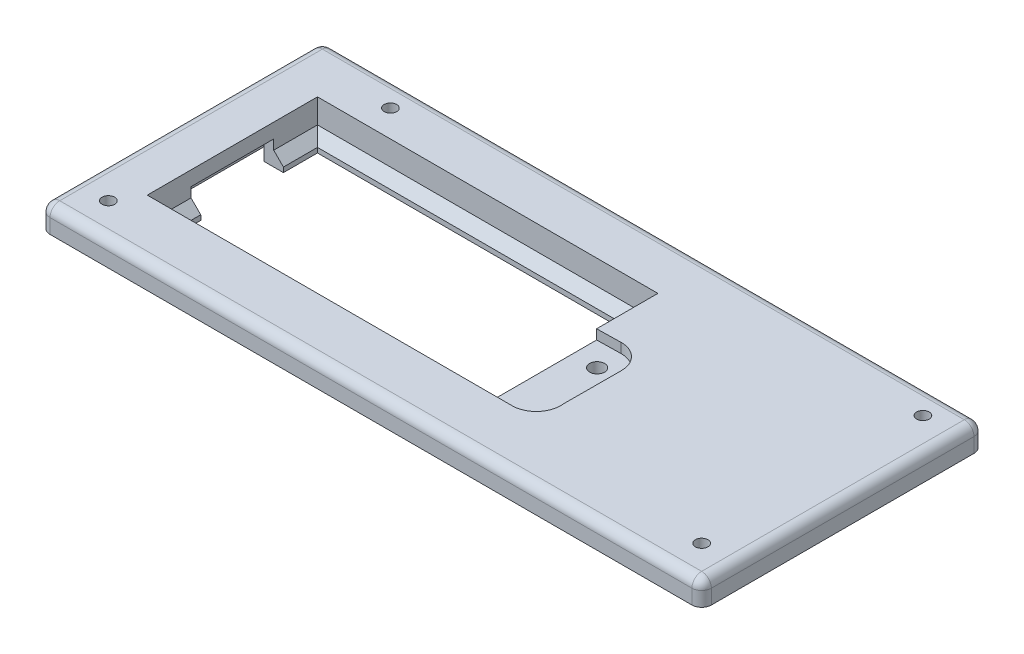
SolidWorks part; units mm, degrees
ref_plane "Front Plane" through (0, 0, 0) normal (0, 0, 1) x (1, 0, 0)
ref_plane "Top Plane" through (0, 0, 0) normal (0, 1, 0) x (1, 0, 0)
ref_plane "Right Plane" through (0, 0, 0) normal (1, 0, 0) x (0, 0, -1)
sketch "Sketch1" plane through (0, 0, 0) normal (0, 1, 0) x (1, 0, 0)
  line L1 (0, 73.66) -> (172.72, 73.66)
  line L2 (0, 73.66) -> (0, 0)
  line L3 (0, 0) -> (172.72, 0)
  line L4 (172.72, 73.66) -> (172.72, 0)
  circle A0 centre (24.765, 66.675) radius 1.6319
  circle A1 centre (8.89, 8.89) radius 1.6319
  circle A2 centre (163.83, 66.675) radius 1.632
  circle A4 centre (163.83, 8.89) radius 1.632
  dimension "D3" = 3.2639
  dimension "D4" = 0
  dimension "D5" = 0
  dimension "D13" = 6.985
  dimension "D14" = 24.765
  dimension "D1" = 172.72
  dimension "D2" = 73.66
  dimension "D7" = 8.89
  dimension "D8" = 8.89
  dimension "D9" = 8.89
  dimension "D10" = 8.89
  dimension "D11" = 6.985
  dimension "D12" = 8.89
extrude "Boss-Extrude1" add sketch "Sketch1" along normal blind 6.35
sketch "Sketch2" plane through (0, 6.35, 0) normal (0, 1, 0) x (1, 0, 0)
  line L0 (172.72, 73.66) -> (0, 73.66) construction
  line L1 (101.6, 59.69) -> (12.7, 59.69)
  line L2 (101.6, 59.69) -> (101.6, 15.24)
  line L3 (101.6, 15.24) -> (12.7, 15.24)
  line L4 (12.7, 59.69) -> (12.7, 15.24)
  line L5 (0, 73.66) -> (0, 0) construction
  dimension "D1" = 44.45
  dimension "D2" = 13.97
  dimension "D3" = 88.9
  dimension "D4" = 12.7
extrude "Cut-Extrude1" cut sketch "Sketch2" against normal blind 6.35
fillet "Fillet1" radius 2.54 8 edges at (172.72, 3.175, -73.66) (172.72, 3.175, 0) (172.72, 6.35, -36.83) (0, 3.175, 0) (86.36, 6.35, 0) (0, 6.35, -36.83) (86.36, 6.35, -73.66) (0, 3.175, -73.66)
sketch "Sketch3" plane through (0, 0, 0) normal (0, -1, 0) x (1, 0, 0)
  line L0 (12.7, -15.24) -> (101.6, -15.24) construction
  line L1 (10.16, -12.7) -> (104.14, -12.7)
  line L3 (15.24, -17.78) -> (104.14, -17.78)
  line L4 (104.14, -12.7) -> (104.14, -17.78)
  line L5 (10.16, -62.23) -> (104.14, -62.23)
  line L6 (10.16, -62.23) -> (10.16, -48.26)
  line L7 (15.24, -57.15) -> (104.14, -57.15)
  line L8 (104.14, -62.23) -> (104.14, -57.15)
  line L9 (101.6, -59.69) -> (12.7, -59.69) construction
  line L10 (12.7, -59.69) -> (12.7, -15.24) construction
  line L11 (12.7, -59.69) -> (12.7, -15.24) construction
  line L14 (10.16, -26.67) -> (15.24, -26.67)
  line L15 (15.24, -17.78) -> (15.24, -26.67)
  line L18 (10.16, -48.26) -> (15.24, -48.26)
  line L19 (15.24, -57.15) -> (15.24, -48.26)
  line L22 (10.16, -26.67) -> (10.16, -12.7)
  dimension "D1" = 2.54
  dimension "D2" = 2.54
  dimension "D3" = 2.54
  dimension "D4" = 2.54
  dimension "D5" = 2.54
  dimension "D6" = 2.54
  dimension "D7" = 93.98
  dimension "D9" = 8.89
  dimension "D10" = 8.89
  dimension "D11" = 2.54
  dimension "D12" = 2.54
extrude "Boss-Extrude2" add sketch "Sketch3" along normal blind 3.81
chamfer "Chamfer1" distance 2.54 angle 45 1 edges at (12.7, 0, -37.465)
chamfer "Chamfer2" distance 2.54 angle 45 4 edges at (58.42, 0, -17.78) (15.24, 0, -22.225) (15.24, 0, -52.705) (58.42, 0, -57.15)
sketch "Sketch6" plane through (0, 6.35, 0) normal (0, 1, 0) x (1, 0, 0)
  line L0 (101.6, 15.24) -> (101.6, 59.69) construction
  line L1 (101.6, 59.69) -> (12.7, 59.69) construction
  line L2 (107.9711, 43.815) -> (107.9289, 43.815)
  line L3 (114.25, 22.385) -> (114.2999, 37.4228)
  line L4 (101.6, 37.465) -> (101.6, 21.5899)
  line L6 (107.5751, 15.2509) -> (108.3484, 15.2524)
  line L7 (107.9711, 43.815) -> (107.9289, 43.815)
  arc A0 (114.2999, 37.4228) -> (101.6, 37.465) centre (107.95, 37.465) ccw
  arc A1 (101.6, 21.5899) -> (114.25, 22.385) centre (107.95, 21.5899) ccw
  point P3 (101.6, 29.5274)
  line M9 (101.6, 59.69) -> (101.6, 15.24)
  dimension "D1" = 6.35
  dimension "D4" = 12.7
  dimension "D5" = 12.6736
  dimension "D2" = 15.0377
  dimension "D3" = 22.225
  dimension "D6" = 6.35
extrude "Cut-Extrude3" cut sketch "Sketch6" against normal blind 2.54 and the other way through all contours L6 A1 L3 A0 L2 M9 region at (107.9425, 6.35, -29.5304)
sketch "Sketch7" plane through (0, 6.35, 0) normal (0, 1, 0) x (1, 0, 0)
  line L0 (101.6, 37.465) -> (101.6, 43.6852)
  line L1 (101.6, 37.465) -> (101.6, 59.69) construction
  line L2 (101.6, 43.6852) -> (107.9711, 43.815)
  line L3 (101.6, 21.5899) -> (101.6, 15.24)
  line L4 (101.6, 15.24) -> (107.95, 15.2524)
  arc A0 (107.9711, 43.815) -> (101.6, 37.465) centre (107.95, 37.465) ccw
  arc A2 (114.2999, 37.4228) -> (107.9711, 43.815) centre (107.95, 37.465) ccw construction
  arc M2 (107.5751, 15.2509) -> (101.6, 21.5899) centre (107.95, 21.5899) cw
  line M3 (101.6, 21.5899) -> (101.6, 15.24)
  line M7 (101.6, 59.69) -> (101.6, 37.465)
  arc M8 (101.6, 37.465) -> (107.9289, 43.815) centre (107.95, 37.465) cw
  dimension "D1" = 12.7
  dimension "D2" = 0
extrude "Cut-Extrude4" cut sketch "Sketch7" against normal blind 2.54 and the other way through all contours L2 M7 M8 | L4 M3 M2 region at (102.9832, 6.35, -42.3276) region at (103.0071, 6.35, -16.6643)
sketch "Sketch8" plane through (0, 0, 0) normal (0, -1, 0) x (1, 0, 0)
  line L0 (10.16, -37.465) -> (101.6, -37.465) construction
  line L1 (10.16, -48.26) -> (10.16, -26.67) construction
  line L2 (101.6, -17.78) -> (101.6, -57.15) construction
  circle A0 centre (107.95, -37.465) radius 5.08
  dimension "D1" = 10.16
  dimension "D2" = 0
  dimension "D3" = 6.35
extrude "Boss-Extrude3" add sketch "Sketch8" along normal blind 2.54
sketch "Sketch9" plane through (0, -2.54, 0) normal (0, -1, 0) x (1, 0, 0)
  circle A0 centre (107.95, -37.465) radius 1.9685
  circle A1 centre (107.95, -37.465) radius 5.08 construction
  circle A2 centre (107.95, -37.465) radius 5.08 construction
  dimension "D3" = 3.937
  dimension "D1" = 0
  dimension "D2" = 0
extrude "Cut-Extrude5" cut sketch "Sketch9" against normal blind 6.35
sketch "Sketch10" plane through (0, 0, 0) normal (0, -1, 0) x (1, 0, 0)
  line L0 (170.18, -73.66) -> (2.54, -73.66) construction
  line L1 (19.05, -4.318) -> (153.67, -4.318)
  line L2 (19.05, -4.318) -> (19.05, -6.858)
  line L3 (19.05, -6.858) -> (153.67, -6.858)
  line L4 (153.67, -4.318) -> (153.67, -6.858)
  line L5 (165.862, -19.05) -> (168.402, -19.05)
  line L6 (165.862, -19.05) -> (165.862, -54.61)
  line L7 (165.862, -54.61) -> (168.402, -54.61)
  line L8 (168.402, -19.05) -> (168.402, -54.61)
  line L9 (4.318, -19.05) -> (6.858, -19.05)
  line L10 (4.318, -19.05) -> (4.318, -71.247)
  line L11 (4.318, -71.247) -> (6.858, -71.247)
  line L12 (6.858, -19.05) -> (6.858, -71.247)
  line L13 (6.858, -71.247) -> (13.208, -71.247)
  line L14 (6.858, -71.247) -> (6.858, -68.707)
  line L15 (6.858, -68.707) -> (13.208, -68.707)
  line L16 (13.208, -71.247) -> (13.208, -68.707)
  line L17 (39.37, -71.247) -> (153.67, -71.247)
  line L18 (39.37, -71.247) -> (39.37, -68.707)
  line L19 (39.37, -68.707) -> (153.67, -68.707)
  line L20 (153.67, -71.247) -> (153.67, -68.707)
  line L21 (2.54, 0) -> (170.18, 0) construction
  line L22 (172.72, -2.54) -> (172.72, -71.12) construction
  line L23 (0, -71.12) -> (0, -2.54) construction
  dimension "D1" = 2.413
  dimension "D2" = 4.318
  dimension "D3" = 4.318
  dimension "D4" = 4.318
  dimension "D5" = 2.413
  dimension "D6" = 2.54
  dimension "D7" = 2.54
  dimension "D8" = 2.54
  dimension "D9" = 2.54
  dimension "D10" = 2.54
  dimension "D11" = 19.05
  dimension "D12" = 19.05
  dimension "D13" = 19.05
  dimension "D14" = 19.05
  dimension "D15" = 19.05
  dimension "D16" = 19.05
  dimension "D17" = 114.3
  dimension "D18" = 6.35
extrude "Boss-Extrude4" add sketch "Sketch10" along normal blind 3.81 contours L4 L1 L2 L3 | L17 L20 L19 L18 | L8 L5 L6 L7 | L12 L9 L10 L11 | L13 L16 L15 L14 region at (86.36, 0, -5.588) region at (167.132, 0, -36.83) region at (5.588, 0, -45.1485) region at (96.52, 0, -69.977)
fillet "Fillet2" radius 2.54 1 edges at (4.318, -1.905, -71.247)
